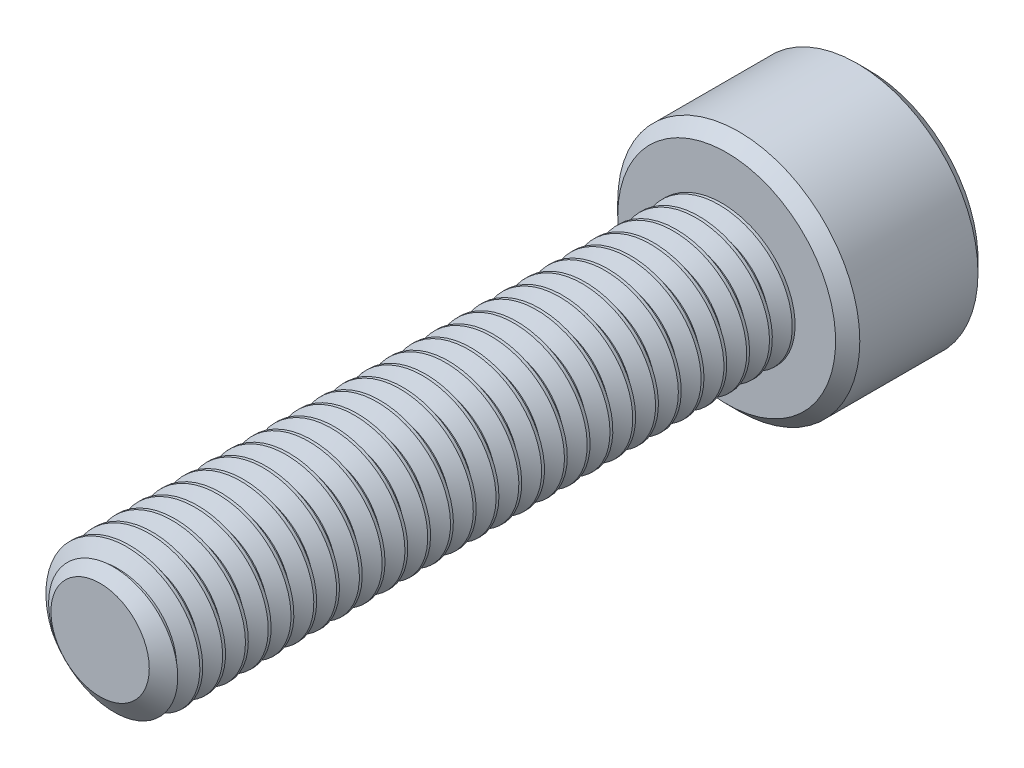
SolidWorks part; units mm, degrees
note: '?' marks a value the reader was unsure of.
ref_plane "Front Plane" through (0, 0, 0) normal (0, 0, 1) x (1, 0, 0)
ref_plane "Top Plane" through (0, 0, 0) normal (0, 1, 0) x (1, 0, 0)
ref_plane "Right Plane" through (0, 0, 0) normal (1, 0, 0) x (0, 0, -1)
sketch "Sketch1" plane through (0, 0, 0) normal (0, 0, 1) x (1, 0, 0)
  circle A0 centre (0, 0) radius 2.5
  dimension "OD" = 5
extrude "Extrude1" add sketch "Sketch1" against normal blind 22
sketch "Sketch2" plane through (0, 0, 0) normal (0, 0, 1) x (1, 0, 0)
  circle A0 centre (0, 0) radius 2.5 construction
  circle A1 centre (0, 0) radius 2.5
curve "Helix/Spiral1" pitch 0.8 height 22.8 turns 28.5 parameters "pitch"=0.8
sketch "Sketch3" plane through (0, 0, 0) normal (1, 0, 0) x (0, 0, -1)
  line L0 (-0.7, 2.5) -> (-0.4, 1.9804)
  line L1 (-0.4, 1.9804) -> (-0.3, 1.9804)
  line L2 (-0.3, 1.9804) -> (0, 2.5)
  line L3 (-0.7, 2.5) -> (0, 2.5)
  line L4 (-0.35, 2.5) -> (-0.35, 1.9804) construction
  line L5 (-0.55, 2.2402) -> (-0.15, 2.2402) construction
  line L6 (0, 2.5) -> (0, -2.5) construction
  dimension "D1" = 0.1
  dimension "D2" = 0.4
  dimension "D3" = 60
sweep "Cut-Sweep1" cut profiles "Sketch3" path "Helix/Spiral1"
sketch "Sketch4" plane through (0, 0, 0) normal (1, 0, 0) x (0, 0, -1)
  line L0 (0.5417, 2.5) -> (0, 1.7264)
  line L1 (0, 1.7264) -> (0, 2.5)
  line L2 (0.5417, 2.5) -> (0, 2.5)
  line L3 (-0.7, 2.5) -> (0, 2.5) construction
  line L4 (0, 0) -> (7.0209, 0) construction
  dimension "D1" = 55
  dimension "D2" = 0.254
revolve "Cut-Revolve1" cut sketch "Sketch4" angle 360 about L4
sketch "Sketch6" plane through (0, 0, -22) normal (0, 0, -1) x (-1, 0, 0)
  circle A0 centre (0, 0) radius 4.25
  dimension "head dia" = 8.5
extrude "Extrude2" add sketch "Sketch6" along normal blind 5
sketch "Sketch7" plane through (0, 0, -27) normal (0, 0, -1) x (-1, 0, 0)
  line L1 (0, 2.3094) -> (-2, 1.1547)
  line L2 (-2, 1.1547) -> (-2, -1.1547)
  line L3 (-2, -1.1547) -> (0, -2.3094)
  line L4 (0, -2.3094) -> (2, -1.1547)
  line L5 (2, -1.1547) -> (2, 1.1547)
  line L6 (2, 1.1547) -> (0, 2.3094)
  circle A0 centre (0, 0) radius 2 construction
  dimension "hex dia" = 4
extrude "Cut-Extrude1" cut sketch "Sketch7" against normal blind 3
sketch "Sketch8" plane through (0, 0, -27) normal (0, 0, -1) x (-1, 0, 0)
  circle A0 centre (0, 0) radius 2.3094
extrude "Cut-Extrude2" cut sketch "Sketch8" against normal through all draft 45
chamfer "Chamfer1" distance 0.425 angle 45 2 edges at (-4.25, 0, -27) (-4.25, 0, -22)
sketch "Sketch10" plane through (0, 0, -22) normal (0, 0, 1) x (1, 0, 0)
  circle A1 centre (0, 0) radius 2.5
  circle A2 centre (0, 0) radius 2.5
  dimension "D1" = 0
ref_plane "Plane1" through (0, 0, 0) normal (0, 0, 1) x (1, 0, 0)
extrude "partial thread" [suppressed] add sketch "Sketch10" along normal up to surface (36 mm away) separate body
chamfer "Chamfer2" [suppressed] distance 0.1 angle 45
combine bodies "Combine1" [suppressed] operation type? add bodies to combine 107 108
sketch "Sketch9" plane through (0, 0, 0) normal (1, 0, 0) x (0, 0, -1)
  line L0 (0, 2.5) -> (0, -2.5) construction
  line L1 (2, 2.5) -> (2, -2.5) construction
  dimension "D1" = 2
equation "\"D3@Helix/Spiral1\" = \"screw length@Extrude1\"+\"pitch@Helix/Spiral1\""
equation "\"D1@Sketch3\" = \"pitch@Helix/Spiral1\"*.125"
equation "\"D2@Sketch3\" = \"pitch@Helix/Spiral1\"*.5"
equation "\"D1@Cut-Extrude1\" = \"hex dia@Sketch7\"*.75"
equation "\"D1@Chamfer1\" = \"head dia@Sketch6\"*.05"
equation "\"D1@Sketch9\" = \"pitch@Helix/Spiral1\"*2.5"
equation "\"D1@Chamfer2\"=\"OD@Sketch1\"*.02"
